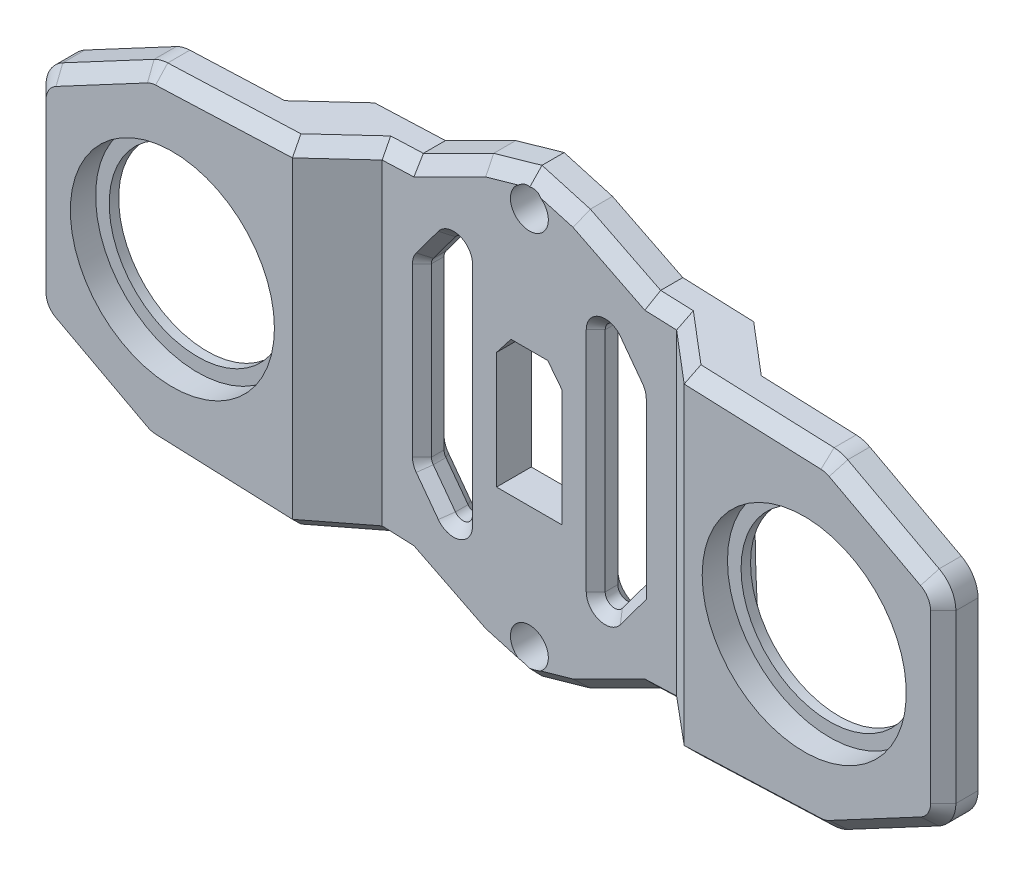
SolidWorks part; units mm, degrees
ref_plane "Front Plane" through (0, 0, 0) normal (0, 0, 1) x (1, 0, 0)
ref_plane "Top Plane" through (0, 0, 0) normal (0, 1, 0) x (1, 0, 0)
ref_plane "Right Plane" through (0, 0, 0) normal (1, 0, 0) x (0, 0, -1)
sketch "Sketch1" plane through (0, 0, 0) normal (0, 0, 1) x (1, 0, 0)
  line L0 (0, 0) -> (-50, 0) construction
  line L1 (0, 0) -> (0, 30) construction
  line L4 (-72, 16.2106) -> (-72, -16.2106)
  line L11 (0, 35) -> (-7.6463, 32.8186)
  line L12 (-7.6463, 32.8186) -> (-18.7809, 27.2508)
  line L13 (-18.7809, 27.2508) -> (-53.8745, 25.8731)
  line L14 (-53.8745, 25.8731) -> (-72, 16.2106)
  line L15 (-53.8745, -25.8731) -> (-72, -16.2106)
  line L16 (-18.7809, -27.2508) -> (-53.8745, -25.8731)
  line L17 (-7.6463, -32.8186) -> (-18.7809, -27.2508)
  line L18 (0, -35) -> (-7.6463, -32.8186)
  line L20 (0, -35) -> (7.6463, -32.8186)
  line L21 (7.6463, -32.8186) -> (18.7809, -27.2508)
  line L22 (18.7809, -27.2508) -> (53.8745, -25.8731)
  line L23 (53.8745, -25.8731) -> (72, -16.2106)
  line L24 (53.8745, 25.8731) -> (72, 16.2106)
  line L25 (18.7809, 27.2508) -> (53.8745, 25.8731)
  line L26 (7.6463, 32.8186) -> (18.7809, 27.2508)
  line L27 (0, 35) -> (7.6463, 32.8186)
  line L28 (72, 16.2106) -> (72, -16.2106)
  circle A0 centre (0, 30) radius 3
  circle A1 centre (-50, 0) radius 16.15
  circle A2 centre (0, -30) radius 3
  circle A4 centre (50, 0) radius 16.15
  point P13 (-72, 0)
  point P18 (72, 0)
  point P22 (0, -35)
  dimension "D1" = 6
  dimension "D3" = 32.3
  dimension "D2" = 50
  dimension "D4" = 60
  dimension "D5" = 72
extrude "Boss-Extrude1" add sketch "Sketch1" along normal blind 12
sketch "Sketch2" plane through (0, 0, 0) normal (0, 1, 0) x (1, 0, 0)
  line L0 (-31, -12) -> (-23.3, -5.5)
  line L2 (-23.3, -5.5) -> (4.3946, -5.5)
  line L3 (-31, -12) -> (31, -12)
  line L5 (0, 20.7446) -> (0, -29.3903) construction
  line L6 (-72, 0) -> (-72, -6.5)
  line L8 (-72, -6.5) -> (-37.7, -6.5)
  line L9 (-37.7, -6.5) -> (-30, 0)
  line L10 (-30, 0) -> (-72, 0)
  line L11 (30, 0) -> (72, 0)
  line L12 (37.7, -6.5) -> (30, 0)
  line L13 (72, -6.5) -> (37.7, -6.5)
  line L14 (72, 0) -> (72, -6.5)
  line L15 (23.3, -5.5) -> (4.3946, -5.5)
  line L16 (31, -12) -> (23.3, -5.5)
  line L18 (-72, -12) -> (-72, 0) construction
  line L19 (-53.8745, -12) -> (-72, -12) construction
  line L20 (-7.6463, 0) -> (-18.7809, 0) construction
  line L21 (-18.7809, -12) -> (-53.8745, -12) construction
  point P25 (0, -12)
  dimension "D1" = 62
  dimension "D2" = 5.5
  dimension "D3" = 5.5
  dimension "D4" = 7.7
  dimension "D5" = 42
extrude "Cut-Extrude1" cut sketch "Sketch2" against normal through all both and the other way through all
sketch "Sketch3" plane through (0, 0, 5.5) normal (0, 0, 1) x (1, 0, 0)
  line L0 (5.2, -10.7) -> (-5.2, -10.7)
  line L1 (-5, 10.5) -> (5, 10.5) construction
  line L2 (-5, 10.5) -> (-5, -10.5) construction
  line L3 (-5, -10.5) -> (5, -10.5) construction
  line L4 (5, 10.5) -> (5, -10.5) construction
  line L5 (-5, 10.5) -> (5, -10.5) construction
  line L6 (-5, -10.5) -> (5, 10.5) construction
  line L7 (-5.2, -10.7) -> (-5.2, 7.758)
  line L8 (-5.2, 7.758) -> (-2.9087, 10.7)
  line L9 (-2.9087, 10.7) -> (2.9087, 10.7)
  line L10 (0, 14.3964) -> (0, -14.2533) construction
  line L11 (5.2, -10.7) -> (5.2, 7.758)
  line L12 (5.2, 7.758) -> (2.9087, 10.7)
  point P0 (0, 0)
  point P15 (0, -10.7)
  point P17 (0, 10.7)
  dimension "D1" = 0.2
  dimension "D2" = 0.2
  dimension "D3" = 0.2
  dimension "D4" = 21
  dimension "D5" = 10
extrude "Cut-Extrude2" cut sketch "Sketch3" against normal through all both and the other way through all
sketch "Sketch4" plane through (0, 0, 5.5) normal (0, 0, 1) x (1, 0, 0)
  line L0 (-17, 13.75) -> (-17, -13.75)
  line L1 (-17, -13.75) -> (-10.5, -22.5)
  line L2 (-10.5, -22.5) -> (-10.5, 22.5)
  line L3 (-25.9785, 0) -> (17.2443, 0) construction
  line L4 (0, 18.6228) -> (0, -13.7834) construction
  line L5 (-17, 13.75) -> (-10.5, 22.5)
  line L6 (17, 13.75) -> (10.5, 22.5)
  line L7 (10.5, -22.5) -> (10.5, 22.5)
  line L8 (17, -13.75) -> (10.5, -22.5)
  line L9 (17, 13.75) -> (17, -13.75)
  point P0 (17, 0)
  point P10 (-10.5, 0)
  point P11 (-17, 0)
  point P12 (10.5, 0)
  dimension "D1" = 6.5
  dimension "D2" = 45
  dimension "D3" = 27.5
  dimension "D4" = 10.5
extrude "Cut-Extrude3" cut sketch "Sketch4" against normal through all both and the other way through all
fillet "Fillet1" radius 1.5 7 edges at (17, 13.75, 2.75) (10.5, 22.5, 2.75) (10.5, -22.5, 2.75) (-10.5, -22.5, 2.75) (-17, -13.75, 2.75) (-17, 13.75, 2.75) (-10.5, 22.5, 2.75)
sketch "Sketch5" plane through (0, 0, 6.5) normal (0, 0, 1) x (1, 0, 0)
  line L0 (0, 45.7061) -> (0, -41.975) construction
  circle A0 centre (-50, 0) radius 14
  circle A1 centre (-50, 0) radius 18.0732
  circle A2 centre (50, 0) radius 18.0732
  circle A3 centre (50, 0) radius 14
  dimension "D1" = 28
extrude "Boss-Extrude2" add sketch "Sketch5" along normal blind 1.5
fillet "Fillet2" radius 5 8 edges at (72, -16.2106, 9.25) (72, 16.2106, 9.25) (-72, -16.2106, 9.25) (-72, 16.2106, 9.25) (53.8745, 25.8731, 9.25) (53.8745, -25.8731, 9.25) (-53.8745, -25.8731, 9.25) (-53.8745, 25.8731, 9.25)
chamfer "Chamfer1" distance 2 angle 45 34 edges at (-27.15, 26.9222, 8.75) (-21.0404, 27.1621, 5.5) (-13.2136, 30.0347, 5.5) (-3.8231, 33.9093, 5.5) (3.8231, 33.9093, 5.5) (13.2136, 30.0347, 5.5) (21.0404, 27.1621, 5.5) (27.15, 26.9222, 8.75) (41.8648, 26.3446, 12) (62.1188, 21.4782, 12) (72, 0, 12) (62.1188, -21.4782, 12) (41.8648, -26.3446, 12) (27.15, -26.9222, 8.75) (21.0404, -27.1621, 5.5) (13.2136, -30.0347, 5.5) (3.8231, -33.9093, 5.5) (-3.8231, -33.9093, 5.5) (-13.2136, -30.0347, 5.5) (-21.0404, -27.1621, 5.5) (-27.15, -26.9222, 8.75) (-41.8648, -26.3446, 12) (-62.1188, -21.4782, 12) (-72, 0, 12) (-62.1188, 21.4782, 12) (-41.8648, 26.3446, 12) (71.2872, 15.7829, 12) (71.2872, -15.7829, 12) (-71.2872, -15.7829, 12) (-71.2872, 15.7829, 12) (53.8406, 25.748, 12) (53.8406, -25.748, 12) (-53.8406, -25.748, 12) (-53.8406, 25.748, 12)
sketch "Sketch7" plane through (0, 0, 6.5) normal (0, 0, -1) x (-1, 0, 0)
  circle A0 centre (-50, 0) radius 18.5
  circle A1 centre (50, 0) radius 18.5
  dimension "D1" = 37
extrude "Cut-Extrude4" cut sketch "Sketch7" along normal through all
chamfer "Chamfer2" distance 2 angle 45 15 edges at (-17, 0, 0) (-16.9241, -13.7249, 0) (-16.9241, 13.7249, 0) (-14.9541, -16.5041, 0) (-14.9541, 16.5041, 0) (-11.5289, -19.3895, 0) (-11.5289, 19.3895, 0) (-10.5, 0, 0) (15.1021, -16.3049, 0) (11.5289, -19.3895, 0) (10.5, 0, 0) (11.5289, 19.3895, 0) (14.9541, 16.5041, 0) (16.9241, 13.7249, 0) (17, -0.2481, 0)
chamfer "Chamfer3" distance 1.5 angle 45 15 edges at (-17, 0, 5.5) (-16.9241, 13.7249, 5.5) (-16.9241, -13.7249, 5.5) (-14.9541, 16.5041, 5.5) (-14.9541, -16.5041, 5.5) (-11.5289, 19.3895, 5.5) (-11.5289, -19.3895, 5.5) (-10.5, 0, 5.5) (17, -0.2481, 5.5) (16.9241, 13.7249, 5.5) (15.1021, -16.3049, 5.5) (14.9541, 16.5041, 5.5) (11.5289, -19.3895, 5.5) (11.5289, 19.3895, 5.5) (10.5, 0, 5.5)
